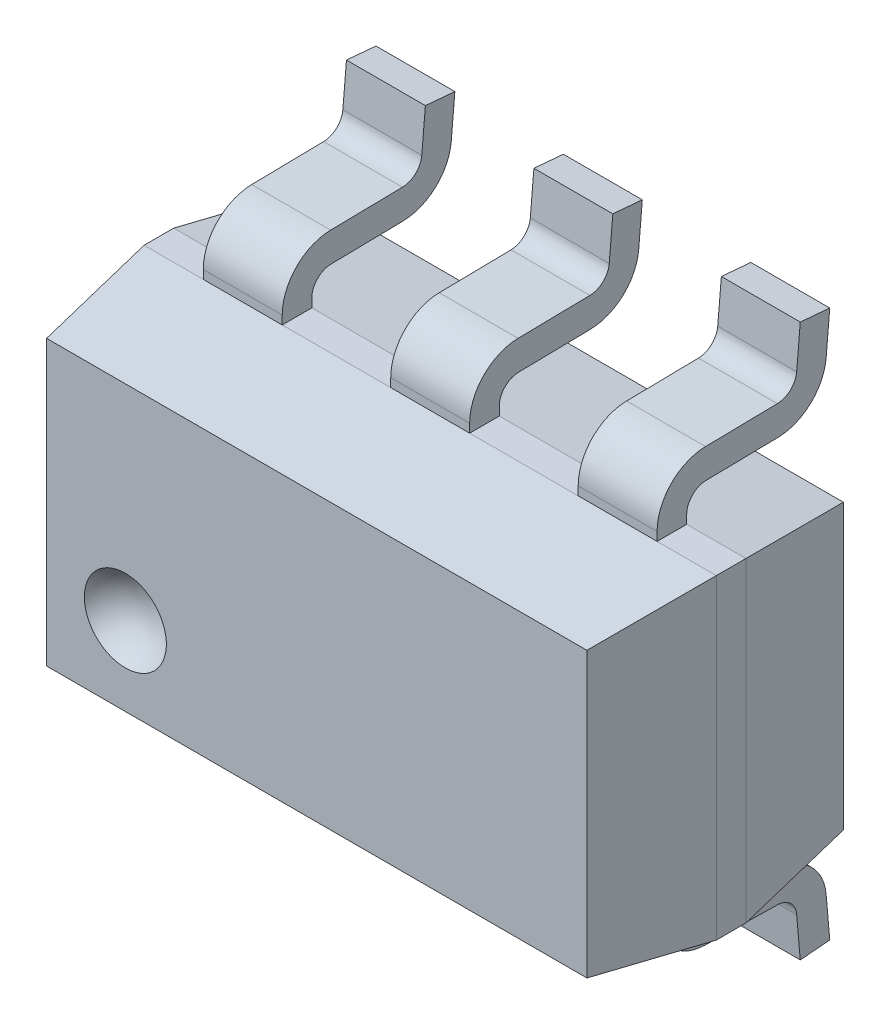
SolidWorks part; units mm, degrees
ref_plane "Top Plane" through (0, 0, 0) normal (0, 0, 1) x (1, 0, 0)
ref_plane "Front Plane" through (0, 0, 0) normal (0, 1, 0) x (1, 0, 0)
ref_plane "Right Plane" through (0, 0, 0) normal (1, 0, 0) x (0, 0, -1)
ref_axis "CenterAxis" through (0, 0, -0.0875) along (0, 0, 1)
ref_plane "Pin1Plane" through (-1.15, 0, 0) normal (1, 0, 0) x (0, 0, -1)
sketch "BodyWxH" plane through (0, 0, 0) normal (1, 0, 0) x (0, 0, -1)
  line L0 (0, 1.54) -> (0, -1.54) construction
  line L1 (-1.45, 0.8) -> (-0.15, 0.8)
  line L2 (-1.45, 0.8) -> (-1.45, -0.8)
  line L3 (-1.45, -0.8) -> (-0.15, -0.8)
  line L4 (-0.15, 0.8) -> (-0.15, -0.8)
  line L6 (-1.45, 0) -> (-0.15, 0) construction
  line L7 (0.0875, 0) -> (-1.8375, 0) construction
  dimension "W" = 1.6
  dimension "SO" = 0.15
  dimension "HMax" = 1.45
extrude "Boss-Body" add sketch "BodyWxH" along normal mid plane 2.9
chamfer "Chamfer1" distance 0.575 angle 8 8 edges at (0, -0.8, 0.15) (1.45, 0, 0.15) (0, 0.8, 0.15) (-1.45, 0, 0.15) (0, 0.8, 1.45) (1.45, 0, 1.45) (0, -0.8, 1.45) (-1.45, 0, 1.45) first distance on face at (0, -0.8, 0.8) first distance on face at (1.45, 0, 0.8) first distance on face at (0, 0.8, 0.8) first distance on face at (-1.45, 0, 0.8)
sketch "LeadCross" plane through (-1.15, 0, 0) normal (1, 0, 0) x (0, 0, -1)
  line L0 (0, -1.3869) -> (-0.1494, -1.4)
  line L1 (-0.1494, -1.4) -> (-0.1677, -1.1912)
  line L2 (-0.2656, -1.1) -> (-0.6294, -1.0936)
  line L3 (-0.875, -0.8437) -> (-0.875, 0.8437)
  line L4 (-0.6294, 1.0936) -> (-0.2656, 1.1)
  line L5 (-0.1677, 1.1912) -> (-0.1494, 1.4)
  line L6 (-0.1494, 1.4) -> (0, 1.3869)
  line L7 (0, 1.3869) -> (-0.0183, 1.1782)
  line L8 (-0.2629, 0.95) -> (-0.6267, 0.9436)
  line L9 (-0.725, 0.8437) -> (-0.725, -0.8437)
  line L10 (-0.6267, -0.9436) -> (-0.2629, -0.95)
  line L11 (-0.0183, -1.1782) -> (0, -1.3869)
  line L12 (0, 1.54) -> (0, -1.54) construction
  line L13 (-0.8, 0) -> (0, 0) construction
  line L14 (0.9625, 0) -> (-0.9625, 0) construction
  line L15 (-0.8, 0.6817) -> (-0.8, -0.6817) construction
  arc A0 (-0.0183, 1.1782) -> (-0.2629, 0.95) centre (-0.2673, 1.2) cw
  arc A1 (-0.2656, 1.1) -> (-0.1677, 1.1912) centre (-0.2673, 1.2) ccw
  arc A2 (-0.2629, -0.95) -> (-0.0183, -1.1782) centre (-0.2673, -1.2) cw
  arc A3 (-0.1677, -1.1912) -> (-0.2656, -1.1) centre (-0.2673, -1.2) ccw
  arc A4 (-0.725, -0.8437) -> (-0.6267, -0.9436) centre (-0.625, -0.8437) ccw
  arc A5 (-0.6294, -1.0936) -> (-0.875, -0.8437) centre (-0.625, -0.8437) cw
  arc A6 (-0.875, 0.8437) -> (-0.6294, 1.0936) centre (-0.625, 0.8437) cw
  arc A7 (-0.6267, 0.9436) -> (-0.725, 0.8437) centre (-0.625, 0.8437) ccw
  dimension "D2" = 5
  dimension "BendRadius" = 0.1
  dimension "LeadThickness" = 0.15
  dimension "ToeLength" = 0.45
  dimension "D4" = 89
  dimension "MidPlane" = 0.8
  dimension "LeadSpan" = 2.8
extrude "Pins" add sketch "LeadCross" along normal blind 0.4
pattern_linear "PatternLeads" count 3 along (1, 0, 0) of "Pins"
ref_plane "Pin1MarkPlane" through (-0.97, 0, 0) normal (1, 0, 0) x (0, 0, -1)
sketch "Pin1Indent" plane through (-0.97, 0, 0) normal (1, 0, 0) x (0, 0, -1)
  line L0 (-1.57, -0.08) -> (-1.57, -0.56) construction
  line L1 (0, 1.54) -> (0, -1.54) construction
  line L2 (-1.57, -0.32) -> (-1.33, -0.32) construction
  line L3 (0.9625, 0) -> (-0.9625, 0) construction
  line L4 (-1.57, -0.08) -> (-1.57, -0.56)
  arc A1 (-1.57, -0.56) -> (-1.57, -0.08) centre (-1.57, -0.32) ccw
  dimension "CutHeight" = 1.57
  dimension "CutSize" = 0.48
  dimension "CutOffset" = 0.32
revolve "Cut-Pin1Indent" cut sketch "Pin1Indent" angle 360 mid plane about L4
equation "\"D1@Chamfer1\" = (\"HMax@BodyWxH\"-\"SO@BodyWxH\"-\"LeadThickness@LeadCross\")/2"
equation "\"D1@Pin1Plane\" = (\"D1@PatternLeads\"-1)*\"LeadPitch@PatternLeads\"/2+(\"LeadWidth@Pins\"/2) ' 1st pin edge plane"
equation "\"CutSize@Pin1Indent\" = \"W@BodyWxH\"*0.3 ' Dent radius is half this value"
equation "\"CutOffset@Pin1Indent\" = \"W@BodyWxH\"/2-(\"W@BodyWxH\"*0.3) ' Dent distance from the center line"
equation "\"D1@Pin1MarkPlane\" = \"D1@Boss-Body\"/2-(\"W@BodyWxH\"*0.3) ' Pin 1 dent lies along this plane"
equation "\"CutHeight@Pin1Indent\" = \"HMax@BodyWxH\"+(\"CutSize@Pin1Indent\"/4) ' Dent is cut by sphere this high"
equation "\"MidPlane@LeadCross\" = (\"HMax@BodyWxH\"+\"SO@BodyWxH\")/2"
